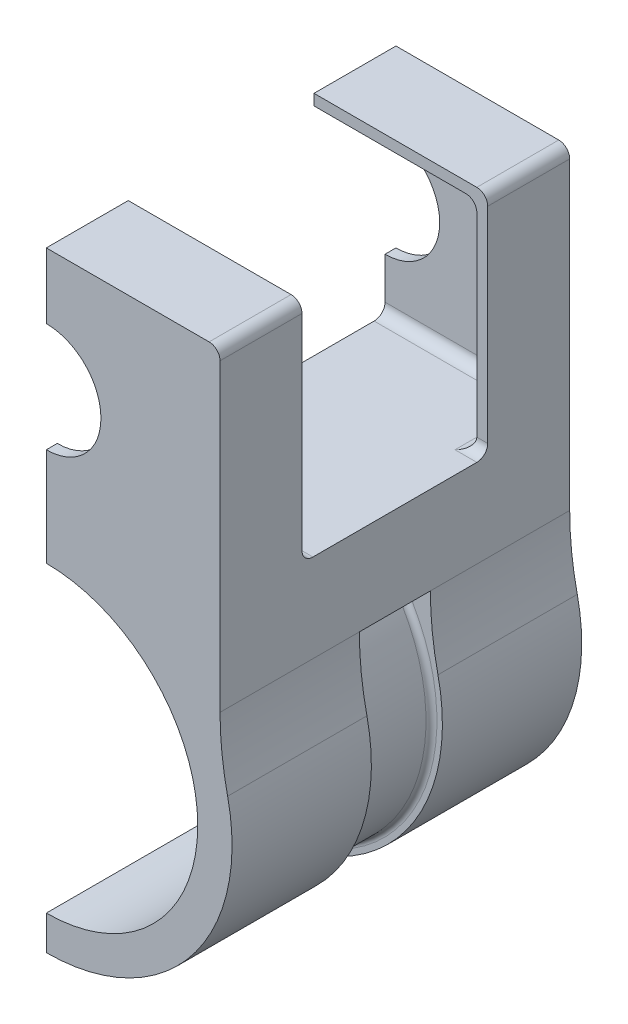
SolidWorks part; units mm, degrees
ref_plane "Front Plane" through (0, 0, 0) normal (0, 0, 1) x (1, 0, 0)
ref_plane "Top Plane" through (0, 0, 0) normal (0, 1, 0) x (1, 0, 0)
ref_plane "Right Plane" through (0, 0, 0) normal (1, 0, 0) x (0, 0, -1)
sketch "Sketch1" plane through (0, 0, 0) normal (0, 0, 1) x (1, 0, 0)
  line L0 (0, 0) -> (0, 52.9844) construction
  line L1 (0, 0) -> (0, -43.18) construction
  line L2 (0, 52.9844) -> (0, 58.0644)
  line L3 (0, 83.4644) -> (0, 98.7044)
  line L4 (0, 98.7044) -> (40.386, 98.7044)
  line L5 (40.386, 98.7044) -> (40.386, 25.3987)
  line L7 (0, 52.9844) -> (0, 35.2044)
  line L8 (0, -35.2044) -> (0, -43.18)
  arc A0 (0, -35.2044) -> (0, 35.2044) centre (0, 0) ccw
  arc A1 (0, -43.18) -> (42.1474, 9.3865) centre (0, 0) ccw
  arc A2 (0, 58.0644) -> (0, 83.4644) centre (0, 70.7644) ccw
  arc A3 (42.1474, 9.3865) -> (40.386, 25.3987) centre (114.046, 25.3987) cw
  dimension "D1" = 70.4088
  dimension "D2" = 86.36
  dimension "D3" = 12.7
  dimension "D8" = 73.66
  dimension "D4" = 5.08
  dimension "D5" = 15.24
  dimension "D6" = 40.386
  dimension "D7" = 17.78
extrude "Boss-Extrude1" add sketch "Sketch1" against normal blind 81.28 contours A2 L3 L4 L5 A3 A1 L8 A0 L7 L2
sketch "Sketch3" plane through (0, 0, 0) normal (-1, 0, 0) x (0, 0, 1)
  line L0 (-78.74, 96.1644) -> (-78.74, 45.8724)
  line L1 (-78.74, 45.8724) -> (-2.54, 45.8724)
  line L2 (-2.54, 45.8724) -> (-2.54, 96.1644)
  line L3 (-2.54, 96.1644) -> (-78.74, 96.1644)
  line L4 (-81.28, 98.7044) -> (0, 98.7044) construction
  line L5 (-81.28, 83.4644) -> (-81.28, 98.7044) construction
  line L6 (0, 83.4644) -> (0, 98.7044) construction
  dimension "D1" = 2.54
  dimension "D2" = 2.54
  dimension "D3" = 2.54
  dimension "D4" = 50.292
extrude "Cut-Extrude1" cut sketch "Sketch3" against normal offset from surface (37.846 mm away) 2.54 up to face at (40.386, 62.0516, -40.64)
sketch "Sketch4" plane through (0, 98.7044, 0) normal (0, 1, 0) x (1, 0, 0)
  line L0 (0, 62.23) -> (40.386, 62.23)
  line L2 (0, 81.28) -> (0, 0) construction
  line L3 (40.386, 81.28) -> (40.386, 0) construction
  line L4 (40.386, 62.23) -> (40.386, 19.05)
  line L5 (40.386, 81.28) -> (40.386, 0) construction
  line L6 (40.386, 19.05) -> (0, 19.05)
  line L7 (0, 19.05) -> (0, 62.23)
  line L8 (0, 81.28) -> (40.386, 81.28) construction
  line L9 (0, 0) -> (40.386, 0) construction
  dimension "D1" = 19.05
  dimension "D2" = 19.05
extrude "Cut-Extrude2" cut sketch "Sketch4" against normal up to surface (52.832 mm away) up to face at (18.923, 45.8724, -40.64)
fillet "Fillet1" radius 2.54 4 edges at (18.923, 45.8724, -78.74) (37.846, 45.8724, -70.485) (18.923, 45.8724, -2.54) (37.846, 45.8724, -10.795)
fillet "Fillet2" radius 2.54 2 edges at (37.846, 96.1644, -70.485) (37.846, 96.1644, -10.795)
fillet "Fillet3" radius 2.54 2 edges at (37.846, 45.8724, -19.05) (37.846, 45.8724, -62.23)
fillet "Fillet4" radius 2.54 2 edges at (40.386, 98.7044, -9.525) (40.386, 98.7044, -71.755)
ref_axis "Axis1" through (0, 0, -81.28) along (0, 0, 1)
ref_plane "Plane1" through (0, -43.18, -81.28) normal (0, 0, 1) x (1, 0, 0)
sketch "Sketch7" plane through (0, 0, 0) normal (-1, 0, 0) x (0, 0, 1)
  line L0 (-81.28, -43.18) -> (0, -43.18) construction
  line L1 (-48.895, -43.18) -> (-32.385, -43.18)
  line L2 (-48.895, -43.18) -> (-48.895, -40.64)
  line L3 (-48.895, -40.64) -> (-32.385, -40.64)
  line L4 (-32.385, -43.18) -> (-32.385, -40.64)
  point P6 (-40.64, -40.64)
  point P7 (-40.64, -43.18)
  dimension "D1" = 16.51
  dimension "D2" = 2.54
revolve "Cut-Revolve2" cut sketch "Sketch7" angle 360 about axis through (0, 0, -81.28) along (0, 0, 1)
ref_plane "Plane2" through (42.1474, 9.3865, 0) normal (0.9761, 0.2174, 0) x (0, 0, -1)
sketch "Sketch8" plane through (42.1474, 9.3865, 0) normal (0.9761, 0.2174, 0) x (0, 0, -1)
  line L0 (81.28, 0) -> (0, 0) construction
  line L1 (32.385, 0) -> (48.895, 0)
  line L2 (32.385, 0) -> (32.385, 16.0122)
  line L3 (32.385, 16.0122) -> (48.895, 16.0122)
  line L4 (48.895, 0) -> (48.895, 16.0122)
  line L5 (81.28, 16.0122) -> (0, 16.0122) construction
  point P8 (40.64, 16.0122)
  point P9 (40.64, 16.0122)
  dimension "D1" = 16.51
extrude "Cut-Extrude4" cut sketch "Sketch8" against normal up to surface and the other way blind 2.54 contours L4 L3 L2 L1 up to face at (20.32, 0, -40.64)
fillet "Fillet5" radius 1.27 2 edges at (40.64, 0, -48.895) (40.64, 0, -32.385)
